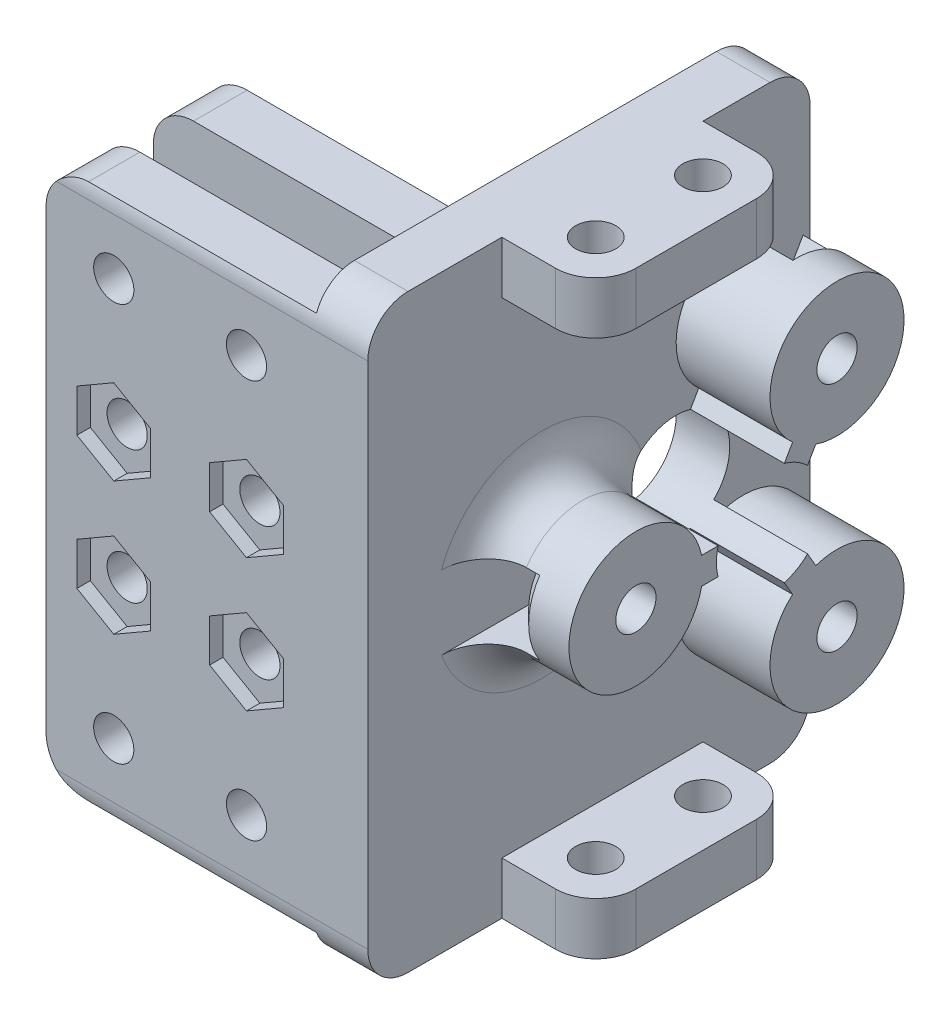
SolidWorks part; units mm, degrees
ref_plane "Спереди" through (0, 0, 0) normal (0, 0, 1) x (1, 0, 0)
ref_plane "Сверху" through (0, 0, 0) normal (0, 1, 0) x (1, 0, 0)
ref_plane "Справа" through (0, 0, 0) normal (1, 0, 0) x (0, 0, -1)
sketch "Sketch1" plane through (0, 0, 0) normal (0, 1, 0) x (1, 0, 0)
  line L5 (-12, -10) -> (12, -10)
  line L6 (-12, -10) -> (-12, 10)
  line L7 (-12, 10) -> (12, 10)
  line L8 (12, -10) -> (12, 10)
  line L9 (-12, -10) -> (12, 10) construction
  line L10 (-12, 10) -> (12, -10) construction
  point P0 (0, 0)
  dimension "D1" = 20
  dimension "D2" = 24
extrude "Boss-Extrude1" add sketch "Sketch1" along normal blind 52.2 contours L5 | L5 region at (0, 0, 0)
sketch "Sketch3" plane through (0, 0, 10) normal (0, 0, 1) x (1, 0, 0)
  line L0 (-12, 52.2) -> (-12, 0) construction
  line L1 (-12, 4) -> (8, 4)
  line L2 (-12, 4) -> (-12, 48.2)
  line L3 (-12, 48.2) -> (8, 48.2)
  line L4 (8, 4) -> (8, 48.2)
  line L5 (-12, 0) -> (12, 0) construction
  line L6 (12, 52.2) -> (12, 0) construction
  line L7 (-12, 52.2) -> (12, 52.2) construction
  dimension "D1" = 4
  dimension "D2" = 4
  dimension "D3" = 4
extrude "Cut-Extrude2" cut sketch "Sketch3" against normal blind 52.2
sketch "Sketch8" plane through (0, 0, 10) normal (0, 0, 1) x (1, 0, 0)
  line L8 (8, 4) -> (-12, 4)
  line L9 (-12, 4) -> (-12, 0)
  line L10 (-12, 0) -> (12, 0)
  line L11 (12, 0) -> (12, 52.2)
  line L12 (12, 52.2) -> (-12, 52.2)
  line L13 (-12, 52.2) -> (-12, 48.2)
  line L14 (-12, 48.2) -> (8, 48.2)
  line L15 (8, 48.2) -> (8, 4)
  line L16 (8, 4) -> (-12, 4)
  line L18 (-12, 0) -> (12, 0)
  line L19 (12, 0) -> (12, 52.2)
  line L20 (12, 52.2) -> (-12, 52.2)
  line L21 (-12, 52.2) -> (-12, 48.2)
  line L22 (-12, 48.2) -> (8, 48.2)
  line L23 (8, 48.2) -> (8, 4)
  line L24 (-12, 4) -> (-12, 0)
  dimension "D1" = 0
extrude "Boss-Extrude3" add sketch "Sketch8" along normal blind 7
sketch "Sketch9" plane through (0, 0, 17) normal (0, 0, 1) x (1, 0, 0)
  line L0 (-12, 0) -> (12, 0) construction
  line L1 (12, 52.2) -> (8, 52.2)
  line L2 (12, 52.2) -> (12, 0)
  line L3 (12, 0) -> (8, 0)
  line L4 (8, 52.2) -> (8, 0)
  dimension "D1" = 4
extrude "Boss-Extrude4" add sketch "Sketch9" along normal blind 6
sketch "Sketch12" plane through (8, 0, 0) normal (-1, 0, 0) x (0, 0, 1)
  line L0 (23, 52.2) -> (23, 0) construction
  line L1 (27, 46.1) -> (19, 46.1)
  line L2 (27, 46.1) -> (27, 6.1)
  line L3 (27, 6.1) -> (19, 6.1)
  line L4 (19, 46.1) -> (19, 6.1)
  line L5 (27, 46.1) -> (19, 6.1) construction
  line L6 (27, 6.1) -> (19, 46.1) construction
  point P0 (23, 26.1)
  line M5 (23, 0) -> (23, 52.2)
  dimension "D1" = 40
  dimension "D2" = 8
extrude "Boss-Extrude5" add sketch "Sketch12" along normal blind 20 contours L1 L4 L3 M5 region at (8, 26.1, 21)
sketch "Sketch13" plane through (0, 0, 23) normal (0, 0, 1) x (1, 0, 0)
  line L0 (8, 46.1) -> (-12, 6.1) construction
  line L1 (2.7339, 26.1) -> (-2.0002, 26.0996) construction
  line L2 (-2.0002, 26.0996) -> (-2.0002, 35.2652) construction
  circle A0 centre (2.9498, 40.95) radius 1.5
  circle A1 centre (2.9523, 11.25) radius 1.5
  circle A2 centre (-6.9527, 11.25) radius 1.5
  circle A3 centre (-6.9502, 40.95) radius 1.5
  dimension "D1" = 3
  dimension "D2" = 9.9
  dimension "D3" = 29.7
extrude "Cut-Extrude6" cut sketch "Sketch13" against normal blind 20
chamfer "Chamfer3" distance 3 angle 45 6 edges at (-2, 0, 17) (-2, 52.2, 17) (10, 52.2, 23) (0, 52.2, -10) (10, 0, 23) (0, 0, -10)
sketch "Sketch14" plane through (12, 0, 0) normal (1, 0, 0) x (0, 0, -1)
  line L0 (0, 52.2) -> (0, 0) construction
  line L1 (-20, 52.2) -> (7, 52.2) construction
  line L2 (-20, 0) -> (7, 0) construction
  line L3 (10, 49.2) -> (10, 3) construction
  circle A1 centre (0, 26.1) radius 4
  circle A2 centre (0, 26.1) radius 8
  dimension "D1" = 10
  dimension "D2" = 8
  dimension "D3" = 4
extrude "Cut-Extrude7" cut sketch "Sketch14" against normal blind 10 contours L0 A1 | A1 L0 region at (12, 26.1, -1.6977) region at (12, 26.1, 1.6977)
sketch "Sketch16" plane through (12, 0, 0) normal (1, 0, 0) x (0, 0, -1)
  line L0 (0, 26.1) -> (-25.7538, 26.1) construction
  circle A0 centre (-10, 26.1) radius 5
  point P12 (0, 26.1)
  dimension "D1" = 10
  dimension "D2" = 10
extrude "Boss-Extrude6" add sketch "Sketch16" along normal blind 7
sketch "Sketch17" plane through (12, 0, 0) normal (1, 0, 0) x (0, 0, -1)
  line L0 (-11.5877, 28.85) -> (-21.3317, 28.85)
  line L1 (-6.8246, 26.1) -> (-8.4123, 28.85)
  line L2 (-8.4123, 28.85) -> (-11.5877, 28.85)
  line L3 (-11.5877, 28.85) -> (-13.1754, 26.1)
  line L4 (-13.1754, 26.1) -> (-11.5877, 23.35)
  line L5 (-11.5877, 23.35) -> (-8.4123, 23.35)
  line L6 (-8.4123, 23.35) -> (-6.8246, 26.1)
  line L7 (-21.3317, 28.85) -> (-21.3317, 23.35)
  line L8 (-21.3317, 23.35) -> (-11.5877, 23.35)
  circle A0 centre (-10, 26.1) radius 2.75 construction
  circle M1 centre (-10, 26.1) radius 5
  dimension "D1" = 5.5
extrude "Cut-Extrude8" cut sketch "Sketch17" along normal blind 3 contours L7 L8 L0 M1 | L5 L6 L1 L2 L3 L4 | L8 L4 L3 L0 M1 region at (12, 26.1, 13.5261) region at (12, 26.1, 10) region at (12, 26.1, 18.0289)
sketch "Sketch18" plane through (19, 0, 0) normal (1, 0, 0) x (0, 0, -1)
  circle A0 centre (-10, 26.1) radius 1.5
  dimension "D1" = 3
extrude "Cut-Extrude9" cut sketch "Sketch18" against normal blind 7
chamfer "Chamfer4" distance 1 angle 45 1 edges at (15, 26.1, 15)
sketch "Sketch19" plane through (12, 0, 0) normal (1, 0, 0) x (0, 0, -1)
  line L1 (-2, 27.1) -> (-6, 27.1)
  line L2 (-2, 27.1) -> (-2, 25.1)
  line L3 (-2, 25.1) -> (-6, 25.1)
  line L4 (-6, 27.1) -> (-6, 25.1)
  line L5 (-2, 27.1) -> (-6, 25.1) construction
  line L6 (-2, 25.1) -> (-6, 27.1) construction
  circle A0 centre (0, 26.1) radius 4 construction
  point P0 (-4, 26.1)
  arc M23 (-14.1758, 28.85) -> (-14.1758, 23.35) centre (-10, 26.1) cw
  circle M28 centre (0, 26.1) radius 4
  dimension "D1" = 2
  dimension "D2" = 4
extrude "Boss-Extrude7" add sketch "Sketch19" along normal blind 7 contours L3 L1 M28 M23 region at (12, 26.1, 4.4955)
pattern_circular "CirPattern1" count 3 over 360 about axis through (2, 26.1, 0) along (1, 0, 0) of "Boss-Extrude6", "Cut-Extrude8", "Cut-Extrude9", "Chamfer4", "Boss-Extrude7" reverse direction yes
sketch "Sketch21" plane through (12, 0, 0) normal (1, 0, 0) x (0, 0, -1)
  line L0 (-20, 0) -> (7, 0) construction
  line L1 (-13, 4) -> (2, 4)
  line L2 (-13, 4) -> (-13, 8)
  line L3 (-13, 8) -> (2, 8)
  line L4 (2, 4) -> (2, 8)
  line L5 (-13, 4) -> (2, 8) construction
  line L6 (-13, 8) -> (2, 4) construction
  line L7 (10, 17.4397) -> (10, 3) construction
  line L8 (0, 26.1) -> (-26.3475, 26.1) construction
  point P0 (-5.5, 6)
  dimension "D1" = 4
  dimension "D2" = 15
  dimension "D3" = 4
  dimension "D4" = 8
extrude "Boss-Extrude8" add sketch "Sketch21" along normal up to surface (7 mm away) up to face at (19, 18.7388, -4.25)
fillet "Fillet3" radius 3 2 edges at (19, 6, 13) (19, 6, -2)
sketch "Sketch22" plane through (0, 4, 0) normal (0, -1, 0) x (1, 0, 0)
  line L0 (19, 5.5) -> (13.2888, 5.5) construction
  line L1 (19, 10) -> (19, 1) construction
  line L2 (12, 20) -> (12, -7) construction
  circle A0 centre (15.5, 9.5) radius 1.5
  circle A2 centre (15.5, 1.5) radius 1.5
  dimension "D1" = 3
  dimension "D2" = 8
  dimension "D3" = 3.5
extrude "Cut-Extrude10" cut sketch "Sketch22" against normal blind 10
sketch "Sketch23" plane through (12, 0, 0) normal (1, 0, 0) x (0, 0, -1)
  line L0 (0, 26.1) -> (13.0368, 26.1) construction
ref_plane "Plane1" through (0, 26.1, 0) normal (0, 1, 0) x (1, 0, 0)
mirror "Mirror1" about plane through (0, 26.1, 0) normal (0, 1, 0) of "Boss-Extrude8", "Fillet3", "Cut-Extrude10"
fillet "Fillet4" radius 3 2 edges at (12, 21.1905, 9.0532) (12, 31.0095, 9.0532)
sketch "Sketch24" plane through (8, 0, 0) normal (-1, 0, 0) x (0, 0, 1)
  line L0 (19, 46.1) -> (19, 6.1) construction
  line L1 (15, 6.1) -> (11, 6.1)
  line L2 (15, 6.1) -> (15, 46.1)
  line L3 (15, 46.1) -> (11, 46.1)
  line L4 (11, 6.1) -> (11, 46.1)
  line L5 (15, 6.1) -> (11, 46.1) construction
  line L6 (15, 46.1) -> (11, 6.1) construction
  point P0 (13, 26.1)
  point P5 (0, 26.1)
  dimension "D1" = 40
  dimension "D2" = 4
  dimension "D3" = 4
extrude "Boss-Extrude9" add sketch "Sketch24" along normal up to surface (20 mm away) up to face at (-12, 26.1, 21)
sketch "Sketch25" plane through (0, 0, 11) normal (0, 0, -1) x (-1, 0, 0)
  line L0 (12, 26.1) -> (2, 26.1) construction
  line L1 (12, 46.1) -> (12, 6.1) construction
  line L2 (2, 26.1) -> (2, 35.1897) construction
  line L3 (-8, 48.2) -> (-8, 4) construction
  circle A0 centre (6.95, 31.05) radius 1.5
  circle A1 centre (6.95, 21.15) radius 1.5
  circle A2 centre (-2.95, 21.15) radius 1.5
  circle A3 centre (-2.95, 31.05) radius 1.5
  dimension "D1" = 3
  dimension "D2" = 9.9
  dimension "D3" = 9.9
extrude "Cut-Extrude11" cut sketch "Sketch25" against normal blind 45
chamfer "Chamfer5" distance 2 angle 45 4 edges at (-8.45, 31.05, 11) (4.45, 31.05, 11) (1.45, 21.15, 11) (-5.45, 21.15, 11)
sketch "Sketch26" plane through (0, 0, 23) normal (0, 0, 1) x (1, 0, 0)
  line L0 (2.95, 17.9746) -> (5.7, 19.5623)
  line L1 (-6.95, 17.9746) -> (-4.2, 19.5623)
  line L2 (-4.2, 19.5623) -> (-4.2, 22.7377)
  line L3 (-4.2, 22.7377) -> (-6.95, 24.3254)
  line L4 (-6.95, 24.3254) -> (-9.7, 22.7377)
  line L5 (-9.7, 22.7377) -> (-9.7, 19.5623)
  line L6 (-9.7, 19.5623) -> (-6.95, 17.9746)
  line L7 (5.7, 19.5623) -> (5.7, 22.7377)
  line L8 (5.7, 22.7377) -> (2.95, 24.3254)
  line L9 (2.95, 24.3254) -> (0.2, 22.7377)
  line L10 (0.2, 22.7377) -> (0.2, 19.5623)
  line L11 (0.2, 19.5623) -> (2.95, 17.9746)
  line L12 (2.95, 27.8746) -> (5.7, 29.4623)
  line L13 (5.7, 29.4623) -> (5.7, 32.6377)
  line L14 (5.7, 32.6377) -> (2.95, 34.2254)
  line L15 (2.95, 34.2254) -> (0.2, 32.6377)
  line L16 (0.2, 32.6377) -> (0.2, 29.4623)
  line L17 (0.2, 29.4623) -> (2.95, 27.8746)
  line L18 (-6.95, 27.8746) -> (-4.2, 29.4623)
  line L19 (-4.2, 29.4623) -> (-4.2, 32.6377)
  line L20 (-4.2, 32.6377) -> (-6.95, 34.2254)
  line L21 (-6.95, 34.2254) -> (-9.7, 32.6377)
  line L22 (-9.7, 32.6377) -> (-9.7, 29.4623)
  line L23 (-9.7, 29.4623) -> (-6.95, 27.8746)
  circle A0 centre (-6.95, 21.15) radius 2.75 construction
  dimension "D1" = 5.5
  dimension "D2" = 2
  dimension "D3" = 2
extrude "Cut-Extrude12" cut sketch "Sketch26" against normal blind 1
sketch "Sketch27" plane through (-12, 0, 0) normal (-1, 0, 0) x (0, 0, 1)
  line L0 (-7, 0) -> (14, 0) construction
  line L1 (14, 0) -> (17, 3) construction
  line L2 (17, 3) -> (17, 4) construction
  line L3 (17, 4) -> (-10, 4) construction
  line L4 (-10, 4) -> (-10, 3) construction
  line L5 (-10, 3) -> (-7, 0) construction
  line L6 (17, 48.2) -> (17, 49.2) construction
  line L7 (17, 49.2) -> (14, 52.2) construction
  line L8 (14, 52.2) -> (-7, 52.2) construction
  line L9 (-7, 52.2) -> (-10, 49.2) construction
  line L10 (-10, 49.2) -> (-10, 48.2) construction
  line L11 (-10, 48.2) -> (17, 48.2) construction
  line L12 (-7, 0) -> (14, 0)
  line L13 (14, 0) -> (17, 3)
  line L14 (17, 3) -> (17, 4)
  line L15 (17, 4) -> (-10, 4)
  line L16 (-10, 4) -> (-10, 3)
  line L17 (-10, 3) -> (-7, 0)
  line L18 (17, 48.2) -> (17, 49.2)
  line L19 (17, 49.2) -> (14, 52.2)
  line L20 (14, 52.2) -> (-7, 52.2)
  line L21 (-7, 52.2) -> (-10, 49.2)
  line L22 (-10, 49.2) -> (-10, 48.2)
  line L23 (-10, 48.2) -> (17, 48.2)
extrude "Cut-Extrude13" cut sketch "Sketch27" against normal blind 20
sketch "Sketch28" plane through (8, 0, 0) normal (-1, 0, 0) x (0, 0, 1)
  line L0 (23, 4.1) -> (-10, 4.1)
  line L1 (11, 6.1) -> (15, 6.1) construction
  line L2 (23, 6.1) -> (23, 3) construction
  line L3 (-10, 49.2) -> (-10, 3) construction
  line L4 (0, 26.1) -> (-15.8704, 26.1) construction
  line L5 (23, 48.1) -> (-10, 48.1)
  line M2 (23, 46.1) -> (23, 49.2)
  line M3 (23, 49.2) -> (20, 52.2)
  line M4 (20, 52.2) -> (-7, 52.2)
  line M5 (-7, 52.2) -> (-10, 49.2)
  line M6 (-10, 49.2) -> (-10, 3)
  line M7 (-10, 3) -> (-7, 0)
  line M8 (-7, 0) -> (20, 0)
  line M9 (20, 0) -> (23, 3)
  line M10 (23, 3) -> (23, 6.1)
  dimension "D1" = 2
extrude "Cut-Extrude14" cut sketch "Sketch28" against normal blind 20 contours L0 M10 M6 M7 M8 M9 | L5 M2 M3 M4 M5 M6 region at (8, 2.1248, 6.5) region at (8, 50.0752, 6.5)
fillet "Fillet5" radius 3 4 edges at (10, 4.1, -10) (10, 48.1, -10) (10, 4.1, 23) (10, 48.1, 23)
fillet "Fillet6" radius 3 4 edges at (-12, 6.1, 13) (-12, 6.1, 20.9142) (-12, 46.1, 20.9142) (-12, 46.1, 13)
